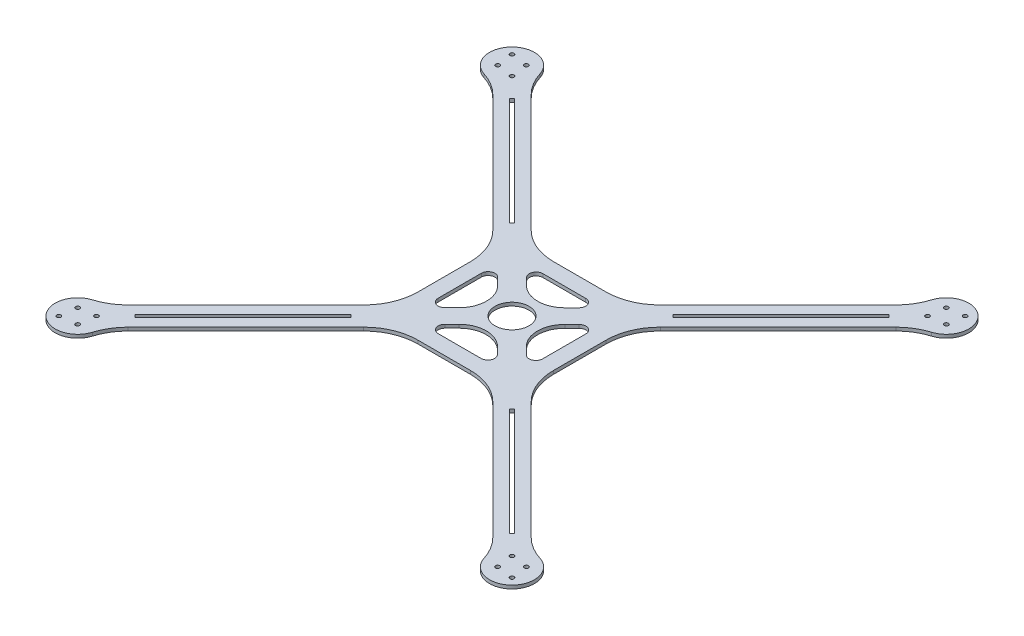
SolidWorks part; units mm, degrees
ref_plane "Front Plane" through (0, 0, 0) normal (0, 0, 1) x (1, 0, 0)
ref_plane "Top Plane" through (0, 0, 0) normal (0, 1, 0) x (1, 0, 0)
ref_plane "Right Plane" through (0, 0, 0) normal (1, 0, 0) x (0, 0, -1)
sketch "Sketch2" plane through (0, 0, 0) normal (0, 1, 0) x (1, 0, 0)
  line L2 (0, 0) -> (355.6, 355.6) construction
  line L3 (-196.4648, 209.9352) -> (-209.9352, 196.4648) construction
  line L4 (-212.0007, 212.0007) -> (-194.3993, 194.3993) construction
  line L5 (209.9352, 196.4648) -> (196.4648, 209.9352) construction
  line L6 (-355.6, 355.6) -> (355.6, 355.6) construction
  line L7 (355.6, -355.6) -> (355.6, 355.6) construction
  line L8 (212.0007, 212.0007) -> (194.3993, 194.3993) construction
  line L9 (-355.6, 355.6) -> (355.6, -355.6) construction
  line L10 (196.4648, -209.9352) -> (209.9352, -196.4648) construction
  line L11 (212.0007, -212.0007) -> (194.3993, -194.3993) construction
  line L12 (-209.9352, -196.4648) -> (-196.4648, -209.9352) construction
  line L13 (-212.0007, -212.0007) -> (-194.3993, -194.3993) construction
  circle A0 centre (203.2, 203.2) radius 152.4 construction
  circle A1 centre (203.2, -203.2) radius 152.4 construction
  circle A2 centre (-203.2, -203.2) radius 152.4 construction
  circle A3 centre (-203.2, 203.2) radius 152.4 construction
  circle A30 centre (-212.0007, 212.0007) radius 1.905
  circle A31 centre (-196.4648, 209.9352) radius 1.905
  circle A32 centre (-194.3993, 194.3993) radius 1.905
  circle A33 centre (-209.9352, 196.4648) radius 1.905
  circle A34 centre (212.0007, 212.0007) radius 1.905
  circle A35 centre (209.9352, 196.4648) radius 1.905
  circle A36 centre (194.3993, 194.3993) radius 1.905
  circle A37 centre (196.4648, 209.9352) radius 1.905
  circle A38 centre (212.0007, -212.0007) radius 1.905
  circle A39 centre (196.4648, -209.9352) radius 1.905
  circle A40 centre (194.3993, -194.3993) radius 1.905
  circle A41 centre (209.9352, -196.4648) radius 1.905
  circle A42 centre (-212.0007, -212.0007) radius 1.905
  circle A43 centre (-209.9352, -196.4648) radius 1.905
  circle A44 centre (-194.3993, -194.3993) radius 1.905
  circle A45 centre (-196.4648, -209.9352) radius 1.905
  point P14 (0, 0)
  point P17 (0, 0)
  point P67 (-203.2, 203.2)
  point P69 (-203.2, 203.2)
  point P101 (0, 0)
  dimension "D1" = 304.8
  dimension "D9" = 3.81
  dimension "D3" = 711.2
  dimension "D6" = 24.892
  dimension "D7" = 19.05
  dimension "D2" = 4
  dimension "D10" = 4
sketch "Sketch3" plane through (0, 0, 0) normal (0, 1, 0) x (1, 0, 0)
  line L0 (-355.6, 355.6) -> (355.6, -355.6) construction
  line L1 (-24.4974, -63.5) -> (24.4974, -63.5)
  line L2 (-63.5, -24.4974) -> (-63.5, 24.4974)
  line L3 (-24.4974, 63.5) -> (24.4974, 63.5)
  line L4 (63.5, -24.4974) -> (63.5, 24.4974)
  line L5 (-63.5, -63.5) -> (63.5, 63.5) construction
  line L6 (-63.5, 63.5) -> (63.5, -63.5) construction
  line L7 (0, 0) -> (355.6, 355.6) construction
  line L8 (60.4185, 78.379) -> (170.5921, 188.5526)
  line L9 (88.2902, 88.2902) -> (188.3826, 188.3826) construction
  line L10 (78.379, 60.4185) -> (188.5526, 170.5921)
  line L11 (60.4185, -78.379) -> (170.5921, -188.5526)
  line L12 (78.379, -60.4185) -> (188.5526, -170.5921)
  line L13 (-78.379, -60.4185) -> (-188.5526, -170.5921)
  line L14 (-60.4185, -78.379) -> (-170.5921, -188.5526)
  line L15 (-60.4185, 78.379) -> (-170.5921, 188.5526)
  line L16 (-78.379, 60.4185) -> (-188.5526, 170.5921)
  arc A0 (209.4127, 183.1871) -> (183.1871, 209.4127) centre (203.2, 203.2) ccw
  arc A1 (60.4185, 78.379) -> (24.4974, 63.5) centre (24.4974, 114.3) cw
  arc A2 (209.4127, 183.1871) -> (188.5526, 170.5921) centre (224.4736, 134.6711) ccw
  arc A3 (183.1871, 209.4127) -> (170.5921, 188.5526) centre (134.6711, 224.4736) cw
  arc A4 (78.379, 60.4185) -> (63.5, 24.4974) centre (114.3, 24.4974) ccw
  arc A5 (60.4185, -78.379) -> (24.4974, -63.5) centre (24.4974, -114.3) ccw
  arc A6 (78.379, -60.4185) -> (63.5, -24.4974) centre (114.3, -24.4974) cw
  arc A7 (183.1871, -209.4127) -> (170.5921, -188.5526) centre (134.6711, -224.4736) ccw
  arc A8 (209.4127, -183.1871) -> (188.5526, -170.5921) centre (224.4736, -134.6711) cw
  arc A9 (183.1871, -209.4127) -> (209.4127, -183.1871) centre (203.2, -203.2) ccw
  arc A10 (-78.379, -60.4185) -> (-63.5, -24.4974) centre (-114.3, -24.4974) ccw
  arc A11 (-60.4185, -78.379) -> (-24.4974, -63.5) centre (-24.4974, -114.3) cw
  arc A12 (-209.4127, -183.1871) -> (-188.5526, -170.5921) centre (-224.4736, -134.6711) ccw
  arc A13 (-183.1871, -209.4127) -> (-170.5921, -188.5526) centre (-134.6711, -224.4736) cw
  arc A14 (-209.4127, -183.1871) -> (-183.1871, -209.4127) centre (-203.2, -203.2) ccw
  arc A15 (-60.4185, 78.379) -> (-24.4974, 63.5) centre (-24.4974, 114.3) ccw
  arc A16 (-78.379, 60.4185) -> (-63.5, 24.4974) centre (-114.3, 24.4974) cw
  arc A17 (-183.1871, 209.4127) -> (-170.5921, 188.5526) centre (-134.6711, 224.4736) ccw
  arc A18 (-209.4127, 183.1871) -> (-188.5526, 170.5921) centre (-224.4736, 134.6711) cw
  arc A19 (-183.1871, 209.4127) -> (-209.4127, 183.1871) centre (-203.2, 203.2) ccw
  point P3 (0, 0)
  point P22 (200.3942, 182.4337)
  point P25 (182.4337, 200.3942)
  point P32 (0, 0)
  point P46 (0, 0)
  point P60 (0, 0)
  point P72 (0, 0)
  dimension "D1" = 41.91
  dimension "D2" = 50.8
  dimension "D4" = 50.8
  dimension "D5" = 50.8
  dimension "D3" = 25.4
  dimension "D6" = 4
extrude "Boss-Extrude1" add sketch "Sketch3" along normal blind 3.175
sketch "Sketch4" plane through (0, 3.175, 0) normal (0, 1, 0) x (1, 0, 0)
  circle A0 centre (194.3993, 194.3993) radius 1.905 construction
  circle A1 centre (209.9352, 196.4648) radius 1.905 construction
  circle A2 centre (212.0007, 212.0007) radius 1.905 construction
  circle A3 centre (196.4648, 209.9352) radius 1.905 construction
  circle A4 centre (194.3993, 194.3993) radius 1.905
  circle A5 centre (209.9352, 196.4648) radius 1.905
  circle A6 centre (212.0007, 212.0007) radius 1.905
  circle A7 centre (196.4648, 209.9352) radius 1.905
extrude "Cut-Extrude1" cut sketch "Sketch4" against normal through all
ref_axis "Axis1" through (0, 5.0006, 0) along (0, -1, 0)
pattern_circular "CirPattern1" count 4 over 360 about axis through (0, 5.0006, 0) along (0, -1, 0) of "Cut-Extrude1"
sketch "Sketch5" plane through (0, 3.175, 0) normal (0, 1, 0) x (1, 0, 0)
  line L0 (75.4342, 75.4342) -> (176.2592, 176.2592) construction
  line L1 (74.2121, 76.6367) -> (175.0469, 177.4716)
  line L2 (76.6367, 74.2121) -> (177.4716, 175.0469)
  line L3 (0, 0) -> (355.6, 355.6) construction
  line L4 (74.2121, 76.6367) -> (76.6367, 74.2121)
  line L5 (175.0469, 177.4716) -> (177.4716, 175.0469)
  circle A2 centre (0, 0) radius 63.5 construction
  circle A3 centre (0, 0) radius 106.68 construction
  point P2 (124.0506, 124.0506)
  dimension "D3" = 127
  dimension "D4" = 213.36
  dimension "D1" = 3.429
  dimension "D2" = 38.1
extrude "Cut-Extrude2" cut sketch "Sketch5" against normal through all
sketch "Sketch8" plane through (0, 3.175, 0) normal (0, 1, 0) x (1, 0, 0)
  line L0 (-38.1846, -24.585) -> (-31.4678, -17.8958)
  line L1 (-20.1423, -48.8141) -> (19.8851, -48.8141)
  line L2 (-49.0155, -20.0856) -> (-49.0155, 20.3445)
  line L3 (-19.8851, 48.8141) -> (20.1423, 48.8141)
  line L4 (49.0155, -20.3445) -> (49.0155, 20.0856)
  line L5 (-49.0155, -48.8141) -> (49.0155, 48.8141) construction
  line L6 (-49.0155, 48.8141) -> (49.0155, -48.8141) construction
  line L7 (-24.6232, -37.9648) -> (-18.0252, -31.3939)
  line L8 (-24.3845, 37.9832) -> (-17.8958, 31.4678)
  line L9 (-38.1661, 24.8254) -> (-31.3939, 18.0252)
  line L10 (38.1846, 24.585) -> (31.4678, 17.8958)
  line L11 (24.6232, 37.9648) -> (18.0252, 31.3939)
  line L12 (24.3845, -37.9832) -> (17.8958, -31.4678)
  line L13 (38.1661, -24.8254) -> (31.3939, -18.0252)
  line L14 (-0.0277, -13.4704) -> (35.316, -48.9599) construction
  line L15 (-13.4704, 0.0277) -> (-48.8141, 35.5173) construction
  line L16 (0.0277, 13.4704) -> (35.5173, 48.8141) construction
  line L17 (-13.4704, 0.0277) -> (-48.9599, -35.316) construction
  line L18 (13.4704, -0.0277) -> (48.8141, -35.5173) construction
  line L19 (0.0277, 13.4704) -> (-35.316, 48.9599) construction
  line L20 (-0.0277, -13.4704) -> (-35.5173, -48.8141) construction
  line L21 (13.4704, -0.0277) -> (48.9599, 35.316) construction
  arc A0 (-18.0252, -31.3939) -> (17.8958, -31.4678) centre (-0.1017, -49.3913) cw
  arc A1 (31.3939, -18.0252) -> (31.4678, 17.8958) centre (49.3913, -0.1017) cw
  arc A2 (18.0252, 31.3939) -> (-17.8958, 31.4678) centre (0.1017, 49.3913) cw
  arc A3 (-31.3939, 18.0252) -> (-31.4678, -17.8958) centre (-49.3913, 0.1017) cw
  arc A4 (-19.8851, 48.8141) -> (-24.3845, 37.9832) centre (-19.8851, 42.4641) ccw
  arc A5 (20.1423, 48.8141) -> (24.6232, 37.9648) centre (20.1423, 42.4641) cw
  arc A6 (19.8851, -48.8141) -> (24.3845, -37.9832) centre (19.8851, -42.4641) ccw
  arc A7 (38.1661, -24.8254) -> (49.0155, -20.3445) centre (42.6655, -20.3445) ccw
  arc A8 (49.0155, 20.0856) -> (38.1846, 24.585) centre (42.6655, 20.0856) ccw
  arc A9 (-20.1423, -48.8141) -> (-24.6232, -37.9648) centre (-20.1423, -42.4641) cw
  arc A10 (-38.1846, -24.585) -> (-49.0155, -20.0856) centre (-42.6655, -20.0856) cw
  arc A11 (-49.0155, 20.3445) -> (-38.1661, 24.8254) centre (-42.6655, 20.3445) cw
  point P0 (0, 0)
  point P25 (0, 0)
  dimension "D3" = 25.4
  dimension "D4" = 6.35
  dimension "D1" = 19.05
  dimension "D2" = 4
extrude "Cut-Extrude4" cut sketch "Sketch8" against normal through all
sketch "Sketch9" plane through (0, 3.175, 0) normal (0, 1, 0) x (1, 0, 0)
  circle A0 centre (0, 0) radius 15.875
  dimension "D1" = 31.75
extrude "Cut-Extrude5" cut sketch "Sketch9" against normal through all and the other way through all
pattern_circular "CirPattern2" count 4 over 360 about axis through (0, 5.0006, 0) along (0, -1, 0) of "Cut-Extrude2"
